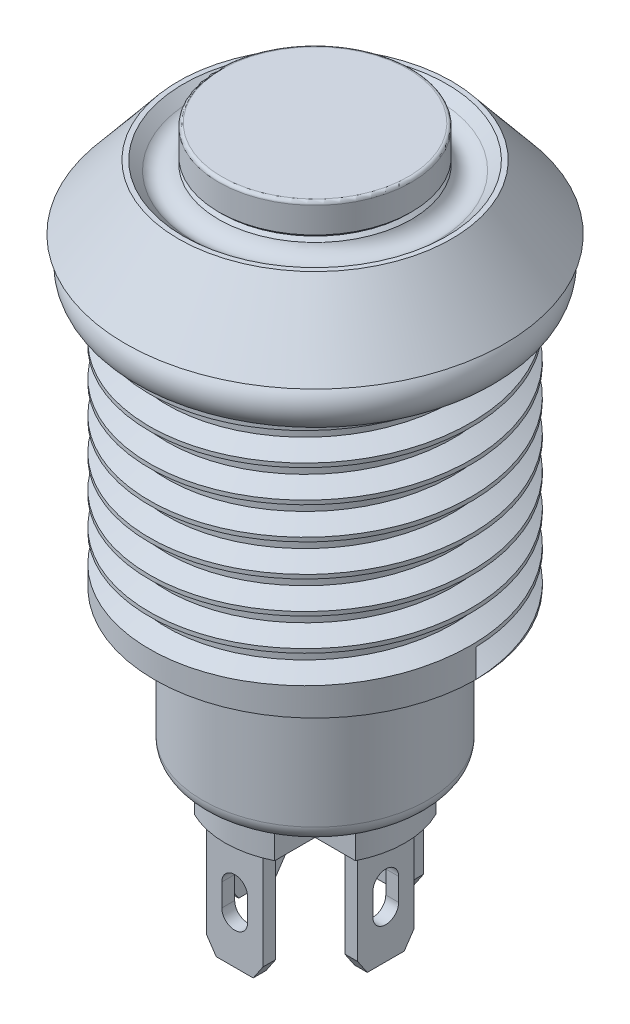
SolidWorks part; units mm, degrees
ref_plane "Front Plane" through (0, 0, 0) normal (0, 0, 1) x (1, 0, 0)
ref_plane "Top Plane" through (0, 0, 0) normal (0, 1, 0) x (1, 0, 0)
ref_plane "Right Plane" through (0, 0, 0) normal (1, 0, 0) x (0, 0, -1)
sketch "Sketch1" plane through (0, 0, 0) normal (0, 1, 0) x (1, 0, 0)
  circle A0 centre (0, 0) radius 5
  dimension "D1" = 10
extrude "Boss-Extrude1" add sketch "Sketch1" along normal blind 10.5
sketch "Sketch3" plane through (0, 0, 0) normal (0, 0, 1) x (1, 0, 0)
  line L0 (0, 10.5) -> (-5.9, 10.5)
  line L1 (5, 10.5) -> (-5, 10.5) construction
  line L2 (-5.9, 10.5) -> (-4.25, 12.5)
  line L3 (-4.25, 12.5) -> (-4.1, 12.5)
  line L4 (0, 11.5) -> (0, 10.5)
  line L5 (0, 10.5) -> (0, 7.9011) construction
  line L6 (0, 11.5) -> (-3, 11.5)
  line L7 (-3, 11.5) -> (-4.1, 12.5)
  dimension "D1" = 8.5
  dimension "D2" = 11.8
  dimension "D3" = 2
  dimension "D4" = 6
  dimension "D5" = 0.15
  dimension "D6" = 1
revolve "Revolve1" add sketch "Sketch3" angle 360 about L5
sketch "Sketch4" plane through (0, 11.5, 0) normal (0, 1, 0) x (1, 0, 0)
  circle A1 centre (0, 0) radius 3
  circle A2 centre (0, 0) radius 3
  dimension "D1" = 0
extrude "Boss-Extrude2" add sketch "Sketch4" along normal blind 1
chamfer "Chamfer1" distance 0.1 angle 45 1 edges at (0, 12.5, 3)
sketch "Sketch5" plane through (0, 12.5, 0) normal (0, 1, 0) x (1, 0, 0)
  circle A0 centre (0, 0) radius 3 construction
  circle A1 centre (0, 0) radius 3
extrude "Boss-Extrude3" add sketch "Sketch5" along normal blind 1
fillet "Fillet1" radius 0.1 1 edges at (0, 13.5, 3)
chamfer "Chamfer2" distance 0.1 angle 45 1 edges at (0, 12.5, 3)
sketch "Sketch6" plane through (0, 0, 0) normal (0, -1, 0) x (1, 0, 0)
  circle A0 centre (0, 0) radius 3.5
  dimension "D1" = 7
extrude "Boss-Extrude4" add sketch "Sketch6" along normal blind 3.5
chamfer "Chamfer4" distance 1 angle 56.5 1 edges at (0, 0, 5)
thread "Thread1" pitch 1 start angle 0, offset 0, length 8, pitch 1, diameter 10
ref_plane "Plane1" through (5, 1, 0) normal (0, 0, 1) x (1, 0, 0)
sketch "Thread Profile1" plane through (5, 1, 0) normal (0, 0, 1) x (1, 0, 0)
  line L0 (0, 0) -> (0, 1) construction
  line L11 (0, 0) -> (0, 0.875)
  line L12 (0, 0.875) -> (-0.5413, 0.5625)
  line L13 (-0.5413, 0.5625) -> (-0.5413, 0.3125)
  line L15 (-0.5413, 0.3125) -> (0, 0)
  line L17 (-0.5413, 0.4375) -> (0, 0.4375) construction
  point P2 (0, 0)
  dimension "Pitch" = 1
  dimension "Profile_Angle" = 60
  dimension "Profile_Land" = 0.25
  dimension "Profile_Height" = 0.5413
sketch "Sketch7" plane through (0, 0, 0) normal (0, 0, 1) x (1, 0, 0)
  line L1 (-5, 10.5) -> (5, 10.5) construction
  line L2 (0, 0) -> (0, 14.8354) construction
  circle A0 centre (5, 9.75) radius 0.75
  dimension "D1" = 1.5
  dimension "D2" = 5
revolve "Revolve2" add sketch "Sketch7" angle 360 about L2
fillet "Fillet2" radius 0.5 1 edges at (0, -3.5, -3.5)
sketch "Sketch10" plane through (0, -3.5, 0) normal (0, -1, 0) x (1, 0, 0)
  line L0 (-2.5055, 1.25) -> (-1.25, 1.25)
  line L1 (1.25, 1.25) -> (2.5055, 1.25)
  line L2 (2.5055, -1.25) -> (1.25, -1.25)
  line L3 (-1.25, 2.5055) -> (-1.25, 1.25)
  line L4 (-1.25, -1.25) -> (-1.25, -2.5055)
  line L5 (1.25, -2.5055) -> (1.25, -1.25)
  line L6 (0, 0) -> (0, 2.0746) construction
  line L7 (0, 0) -> (2.3511, 0) construction
  line L8 (1.25, 1.25) -> (1.25, 2.5055)
  line L9 (-1.25, -1.25) -> (-2.5055, -1.25)
  arc A0 (-2.5055, 1.25) -> (-2.5055, -1.25) centre (0, 0) ccw
  arc A1 (1.25, 2.5055) -> (-1.25, 2.5055) centre (0, 0) ccw
  arc A2 (2.5055, -1.25) -> (2.5055, 1.25) centre (0, 0) ccw
  arc A3 (-1.25, -2.5055) -> (1.25, -2.5055) centre (0, 0) ccw
  dimension "D1" = 5.6
  dimension "D2" = 2.5
extrude "Boss-Extrude5" add sketch "Sketch10" along normal blind 1
sketch "Sketch11" plane through (0, -3.5, 0) normal (0, -1, 0) x (1, 0, 0)
  circle A0 centre (0, 0) radius 2.8
  arc A1 (1.25, 2.5055) -> (-1.25, 2.5055) centre (0, 0) ccw construction
extrude "Boss-Extrude6" add sketch "Sketch11" along normal blind 0.25
ref_plane "Plane2" through (0, -8, 0) normal (0, 1, 0) x (1, 0, 0)
sketch "Sketch12" plane through (0, -8, 0) normal (0, 1, 0) x (1, 0, 0)
  line L0 (0, 0) -> (0, 1.952) construction
  line L1 (0.875, -2.1) -> (-0.875, -2.1)
  line L2 (0.875, -2.1) -> (0.875, -2.5)
  line L3 (0.875, -2.5) -> (-0.875, -2.5)
  line L4 (-0.875, -2.1) -> (-0.875, -2.5)
  line L5 (0.875, -2.1) -> (-0.875, -2.5) construction
  line L6 (0.875, -2.5) -> (-0.875, -2.1) construction
  line L7 (2.2, 0.875) -> (1.8, 0.875) construction
  line L8 (2.2, 0.875) -> (2.2, -0.875) construction
  line L9 (2.2, -0.875) -> (1.8, -0.875) construction
  line L10 (1.8, 0.875) -> (1.8, -0.875) construction
  line L11 (2.2, 0.875) -> (1.8, -0.875) construction
  line L12 (2.2, -0.875) -> (1.8, 0.875) construction
  line L13 (0, 0) -> (1.2217, 0) construction
  line L14 (-2.2, -0.875) -> (-1.8, 0.875) construction
  line L15 (-2.2, 0.875) -> (-1.8, -0.875) construction
  line L16 (-1.8, 0.875) -> (-1.8, -0.875) construction
  line L17 (-2.2, -0.875) -> (-1.8, -0.875) construction
  line L18 (-2.2, 0.875) -> (-2.2, -0.875) construction
  line L19 (-2.2, 0.875) -> (-1.8, 0.875) construction
  line L20 (0.875, 2.5) -> (-0.875, 2.1) construction
  line L21 (0.875, 2.1) -> (-0.875, 2.5) construction
  line L22 (-0.875, 2.1) -> (-0.875, 2.5)
  line L23 (0.875, 2.5) -> (-0.875, 2.5)
  line L24 (0.875, 2.1) -> (0.875, 2.5)
  line L25 (0.875, 2.1) -> (-0.875, 2.1)
  point P0 (0, -2.3)
  point P5 (2, 0)
  point P18 (-2, 0)
  point P23 (0, 2.3)
  dimension "D1" = 1.75
  dimension "D2" = 0.4
  dimension "D3" = 4.4
  dimension "D4" = 5
extrude "Boss-Extrude7" add sketch "Sketch12" along normal up to next
sketch "Sketch16" plane through (0, -8, 0) normal (0, 1, 0) x (1, 0, 0)
  line L0 (2.2, 0.875) -> (1.8, 0.875) construction
  line L1 (2.2, 0.875) -> (2.2, -0.875) construction
  line L2 (2.2, -0.875) -> (1.8, -0.875) construction
  line L3 (1.8, 0.875) -> (1.8, -0.875) construction
  line L4 (-1.8, 0.875) -> (-1.8, -0.875) construction
  line L5 (-2.2, 0.875) -> (-1.8, 0.875) construction
  line L6 (-2.2, 0.875) -> (-2.2, -0.875) construction
  line L7 (-2.2, -0.875) -> (-1.8, -0.875) construction
  line L8 (2.2, 0.875) -> (1.8, 0.875)
  line L9 (2.2, 0.875) -> (2.2, -0.875)
  line L10 (2.2, -0.875) -> (1.8, -0.875)
  line L11 (1.8, 0.875) -> (1.8, -0.875)
  line L12 (-1.8, 0.875) -> (-1.8, -0.875)
  line L13 (-2.2, 0.875) -> (-1.8, 0.875)
  line L14 (-2.2, 0.875) -> (-2.2, -0.875)
  line L15 (-2.2, -0.875) -> (-1.8, -0.875)
extrude "Boss-Extrude9" add sketch "Sketch16" along normal up to next
sketch "Sketch13" plane through (0, -4.5, 0) normal (0, -1, 0) x (1, 0, 0)
  line L0 (0, 0) -> (-2.3528, 0) construction
  text T0 "+      -" font "Century Gothic" height 1
  dimension "D1" = 0.48
  dimension "D2" = 1.84
extrude "Boss-Extrude8" add sketch "Sketch13" along normal blind 0.05
chamfer "Chamfer5" distance 0.3 angle 56 4 edges at (2, -8, 0.875) (2, -8, -0.875) (-2, -8, -0.875) (-2, -8, 0.875)
sketch "Sketch14" plane through (0, 0, 0) normal (1, 0, 0) x (0, 0, -1)
  line L0 (0, -6.6) -> (0, -5.9) construction
  line L1 (-0.4, -6.6) -> (-0.4, -5.9)
  line L2 (0.4, -6.6) -> (0.4, -5.9)
  line L4 (-0.575, -8) -> (0.575, -8) construction
  arc A0 (-0.4, -6.6) -> (0.4, -6.6) centre (0, -6.6) ccw
  arc A1 (0.4, -5.9) -> (-0.4, -5.9) centre (0, -5.9) ccw
  point P2 (0, -6.25)
  dimension "D2" = 1.5
  dimension "D1" = 0.8
  dimension "D3" = 1
sketch "Sketch15" plane through (0, 0, 0) normal (0, 0, 1) x (1, 0, 0)
  line L0 (0, -6.6) -> (0, -5.9) construction
  line L1 (-0.4, -6.6) -> (-0.4, -5.9)
  line L2 (0.4, -6.6) -> (0.4, -5.9)
  line L3 (-0.575, -8) -> (0.575, -8) construction
  arc A0 (-0.4, -6.6) -> (0.4, -6.6) centre (0, -6.6) ccw
  arc A1 (0.4, -5.9) -> (-0.4, -5.9) centre (0, -5.9) ccw
  point P2 (0, -6.25)
  dimension "D2" = 1.5
  dimension "D1" = 0.8
  dimension "D3" = 1
extrude "Cut-Extrude2" cut sketch "Sketch15" against normal through all both and the other way through all
extrude "Cut-Extrude3" cut sketch "Sketch14" against normal through all both and the other way through all
chamfer "Chamfer6" distance 0.3 angle 56 4 edges at (0.875, -8, -2.3) (-0.875, -8, -2.3) (0.875, -8, 2.3) (-0.875, -8, 2.3)
fillet "Fillet3" radius 0.5 1 edges at (0, 11.5, 3)
